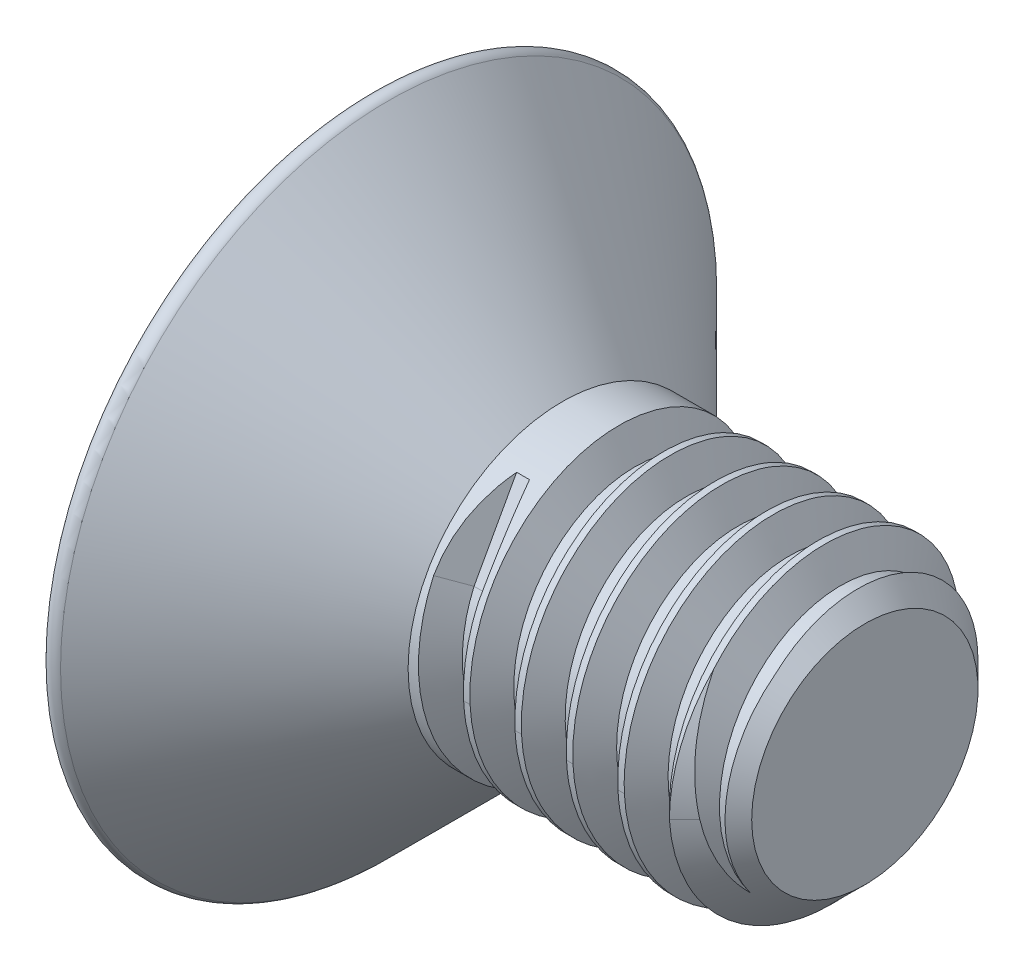
SolidWorks part; units mm, degrees
material "Alloy Steel"
ref_plane "Front Plane" through (0, 0, 0) normal (0, 0, 1) x (1, 0, 0)
ref_plane "Top Plane" through (0, 0, 0) normal (0, 1, 0) x (1, 0, 0)
ref_plane "Right Plane" through (0, 0, 0) normal (1, 0, 0) x (0, 0, -1)
sketch "Sketch2" plane through (0, 0, 0) normal (0, 0, 1) x (1, 0, 0)
  line L0 (0, 0) -> (9.6, 0) construction
  line L1 (0, 0) -> (0, 6.72)
  line L2 (0, 6.72) -> (3.72, 3)
  line L3 (3.72, 3) -> (9.6, 3)
  line L4 (9.6, 3) -> (9.6, 0)
  line L5 (0, 0) -> (9.6, 0)
  point P4 (0, 0)
  dimension "D1" = 5.88
  dimension "D2" = 3.72
  dimension "D3" = 3
  dimension "D4" = 45
  dimension "D5" = 6.72
revolve "Revolve1" add sketch "Sketch2" angle 360 about L0
chamfer "Chamfer1" distance 0.8 angle 45 1 edges at (9.6, 0, 3)
thread "Thread1" pitch 1 start angle 0, offset 3, length 0, pitch 1, diameter 6
ref_plane "Plane1" through (11.8, 0, 3) normal (0, -1, 0) x (0, 0, 1)
sketch "Thread Profile1" plane through (11.8, 0, 3) normal (0, -1, 0) x (0, 0, 1)
  line L0 (0, 0) -> (0, 1) construction
  line L11 (0, 0) -> (0, 0.875)
  line L12 (0, 0.875) -> (-0.5413, 0.5625)
  line L13 (-0.5413, 0.5625) -> (-0.5413, 0.3125)
  line L15 (-0.5413, 0.3125) -> (0, 0)
  line L17 (-0.5413, 0.4375) -> (0, 0.4375) construction
  point P2 (0, 0)
  dimension "Pitch" = 1
  dimension "Profile_Angle" = 60
  dimension "Profile_Land" = 0.25
  dimension "Profile_Height" = 0.5413
sketch "Sketch6" plane through (0, 0, 0) normal (0, -0.8763, 0.4817) x (1, 0, 0)
  line L4 (4.4071, 2.4587) -> (4.7196, 2.9999)
  line L5 (4.7196, 2.9999) -> (3.8446, 2.9999)
  line L6 (3.8446, 2.9999) -> (4.1571, 2.4587)
  line L7 (4.1571, 2.4587) -> (4.4071, 2.4587)
  line L8 (4.4071, 2.4587) -> (4.7196, 2.9999)
  line L9 (4.7196, 2.9999) -> (3.8446, 2.9999)
  line L10 (3.8446, 2.9999) -> (4.1571, 2.4587)
  line L11 (4.1571, 2.4587) -> (4.4071, 2.4587)
  dimension "D1" = 0
extrude "Cut-Extrude1" cut sketch "Sketch6" against normal blind 10
fillet "Fillet1" radius 0.2 1 edges at (0, 0, 6.72)
sketch "Sketch7" plane through (0, 0, 0) normal (-1, 0, 0) x (0, 0, 1)
  line L1 (0, 2.3642) -> (-2.0475, 1.1821)
  line L2 (-2.0475, 1.1821) -> (-2.0475, -1.1821)
  line L3 (-2.0475, -1.1821) -> (0, -2.3642)
  line L4 (0, -2.3642) -> (2.0475, -1.1821)
  line L5 (2.0475, -1.1821) -> (2.0475, 1.1821)
  line L6 (2.0475, 1.1821) -> (0, 2.3642)
  circle A0 centre (0, 0) radius 2.0475 construction
  dimension "D1" = 4.095
extrude "Cut-Extrude2" cut sketch "Sketch7" against normal blind 2.3 draft 3
fillet "Fillet2" radius 0.2 6 edges at (0, 0, -2.0475) (0, -1.7732, -1.0238) (0, -1.7732, 1.0237) (0, 0, 2.0475) (0, 1.7732, 1.0237) (0, 1.7732, -1.0238)
